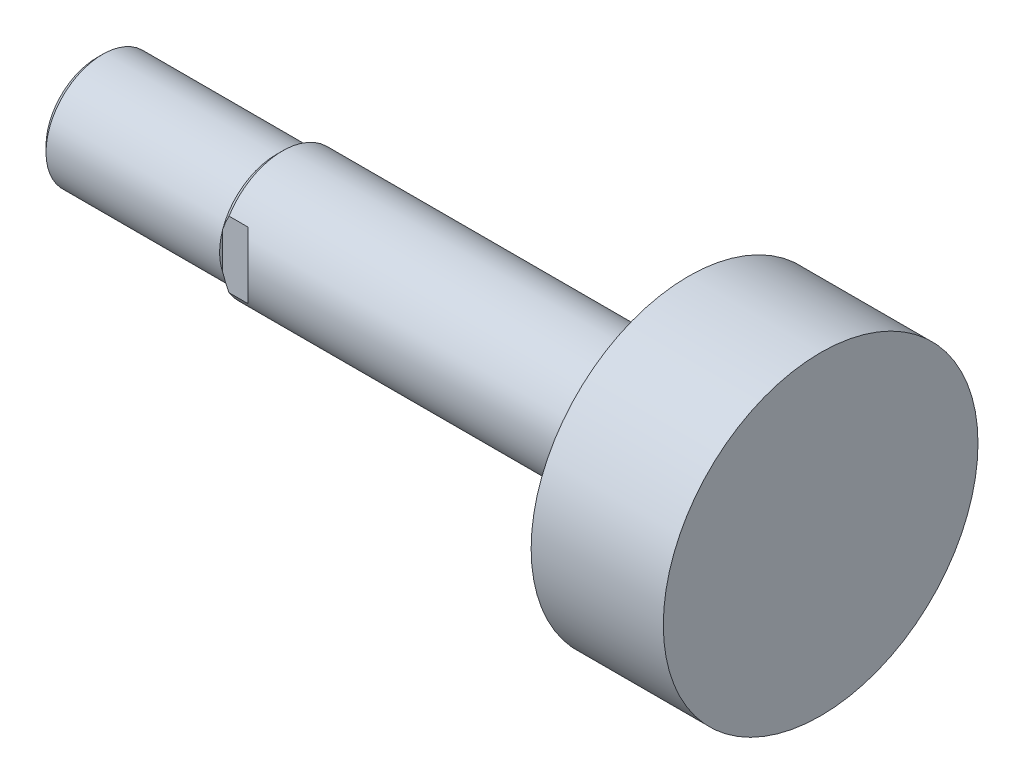
SolidWorks part; units mm, degrees
ref_plane "前视基准面" through (0, 0, 0) normal (0, 0, 1) x (1, 0, 0)
ref_plane "上视基准面" through (0, 0, 0) normal (0, 1, 0) x (1, 0, 0)
ref_plane "右视基准面" through (0, 0, 0) normal (1, 0, 0) x (0, 0, -1)
sketch "草图1" plane through (0, 0, 0) normal (0, 0, 1) x (1, 0, 0)
  line L0 (0, 0) -> (0, 10)
  line L1 (0, 10) -> (60.5, 10)
  line L2 (60.5, 10) -> (60.5, 25)
  line L3 (60.5, 25) -> (81.5, 25)
  line L4 (81.5, 25) -> (81.5, 0)
  line L5 (81.5, 0) -> (0, 0)
  line L6 (81.5, 0) -> (0, 0) construction
revolve "旋转1" add sketch "草图1" angle 360 about L6 reverse direction yes
ref_plane "基准面1" through (-20.5, 0, 0) normal (1, 0, 0) x (0, 0, -1)
ref_plane "基准面2" through (0, 0, 0) normal (1, 0, 0) x (0, 0, -1)
sketch "草图2" plane through (0, 0, 0) normal (0, 0, 1) x (1, 0, 0)
  line L0 (-33.5, 0) -> (-33.5, 8.08)
  line L1 (-33.5, 8.08) -> (-32.58, 9)
  line L2 (-32.58, 9) -> (-5, 9)
  line L3 (-5, 9) -> (-4, 10)
  line L4 (-4, 10) -> (0, 10)
  line L5 (0, 10) -> (0, 0)
  line L6 (0, 0) -> (-33.5, 0)
  line L7 (0, 0) -> (-33.5, 0) construction
revolve "旋转2" add sketch "草图2" angle 360 about L7 reverse direction yes
cosmetic thread "装饰螺纹线1" parameters "D1"=26, "D2"=16.16
sketch "草图3" plane through (0, 0, 0) normal (0, 1, 0) x (1, 0, 0)
  line L0 (-43.5, -28.5) -> (19, -28.5)
  line L1 (19, -28.5) -> (-1, -8.5)
  line L2 (-1, -8.5) -> (-5, -8.5)
  line L3 (-5, -8.5) -> (-5, -18.5)
  line L4 (-5, -18.5) -> (-33.5, -18.5)
  line L5 (-33.5, -18.5) -> (-33.5, 18.5)
  line L6 (-33.5, 18.5) -> (-5, 18.5)
  line L7 (-5, 18.5) -> (-5, 8.5)
  line L8 (-5, 8.5) -> (-1, 8.5)
  line L9 (-1, 8.5) -> (19, 28.5)
  line L10 (19, 28.5) -> (-43.5, 28.5)
  line L11 (-43.5, 28.5) -> (-43.5, -28.5)
extrude "切除-拉伸1" cut sketch "草图3" along normal blind 17 and the other way blind 17
ref_plane "for_nut XY" through (-20.5, 0, 0) normal (-1, 0, 0) x (0, 0, 1)
ref_plane "for_nut XZ" through (0, 0, 0) normal (0, 1, 0) x (1, 0, 0)
ref_plane "for_nut YZ" through (0, 0, 0) normal (0, 0, -1) x (-1, 0, 0)
ref_axis "for_nut X" through (-20.5, 0, 80.9) along (0, 0, -1)
ref_axis "for_nut Y" through (-20.5, 50, 0) along (0, -1, 0)
ref_axis "for_nut Z" through (-80.9, 0, 0) along (1, 0, 0)
sketch3d "for_nut"
  point P0 (-20.5, 0, 0)
ref_plane "rod XY" through (0, 0, 0) normal (1, 0, 0) x (0, 0, -1)
ref_plane "rod XZ" through (0, 0, 0) normal (0, -1, 0) x (-1, 0, 0)
ref_plane "rod YZ" through (0, 0, 0) normal (0, 0, -1) x (-1, 0, 0)
ref_axis "rod X" through (0, 0, 80.9) along (0, 0, -1)
ref_axis "rod Y" through (0, -50, 0) along (0, 1, 0)
ref_axis "rod Z" through (80.9, 0, 0) along (-1, 0, 0)
sketch3d "rod"
  point P0 (0, 0, 0)
